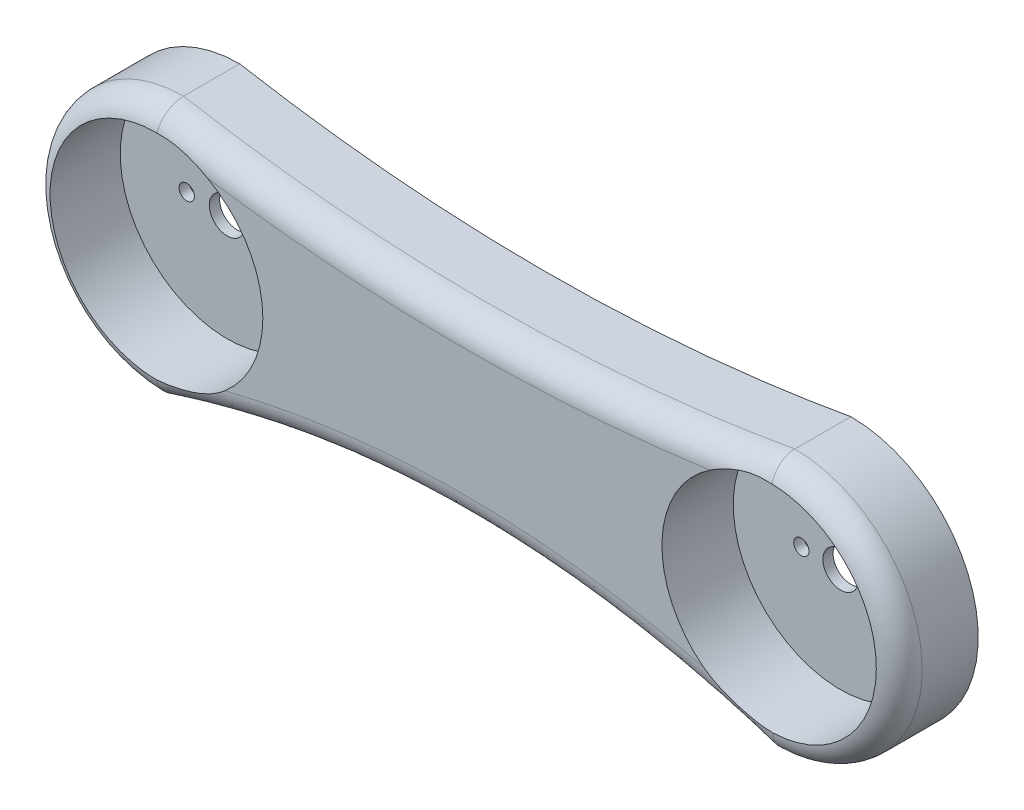
SolidWorks part; units mm, degrees
ref_plane "Front Plane" through (0, 0, 0) normal (0, 0, 1) x (1, 0, 0)
ref_plane "Top Plane" through (0, 0, 0) normal (0, 1, 0) x (1, 0, 0)
ref_plane "Right Plane" through (0, 0, 0) normal (1, 0, 0) x (0, 0, -1)
sketch "Sketch1" plane through (0, 0, 0) normal (0, 0, 1) x (1, 0, 0)
  circle A0 centre (-48.6344, 0) radius 25
  circle A1 centre (71.3656, 0) radius 25
  spline S0 degree 2 poles (-48.6344, 25) (11.2964, 14.3357) (71.3656, 25) knots 0 0 0 1 1 1
  spline S1 degree 2 poles (-48.6344, -25) (11.1374, -5.4597) (71.3656, -25) knots 0 0 0 1 1 1
  dimension "D1" = 50
  dimension "D2" = 50
  dimension "D3" = 120
extrude "Boss-Extrude5" add sketch "Sketch1" along normal blind 16 contours A0 S1 S0 | A0 S1 A1 S0 | A1 S1 S0 region at (-48.6745, 0.0992, 0) region at (11.3768, 2.2252, 0) region at (71.4048, 0.0973, 0)
sketch "Sketch6" plane through (0, 0, 16) normal (0, 0, 1) x (1, 0, 0)
  circle A0 centre (-49.0889, 0) radius 21
  circle A1 centre (71.2705, 0.5496) radius 21
  dimension "D1" = 42
  dimension "D2" = 42
extrude "Cut-Extrude1" cut sketch "Sketch6" against normal blind 14
sketch "Sketch7" plane through (0, 0, 2) normal (0, 0, 1) x (1, 0, 0)
  circle A0 centre (-49.0889, 0) radius 3.5
  circle A1 centre (-57.0323, 0) radius 1.5
  circle A2 centre (-41.7623, 0) radius 1.5
  circle A3 centre (71.3656, 0) radius 3.5
  circle A4 centre (63.6432, 0) radius 1.5
  circle A5 centre (78.9132, 0) radius 1.5
  dimension "D1" = 7
  dimension "D2" = 3
  dimension "D3" = 3
  dimension "D5" = 7
  dimension "D6" = 3
  dimension "D7" = 3
  dimension "D4" = 15.27
  dimension "D8" = 15.27
extrude "Cut-Extrude3" cut sketch "Sketch7" against normal blind 14
fillet "Fillet2" radius 5 4 edges at (-73.6344, 0, 16) (96.3656, 0, 16)
